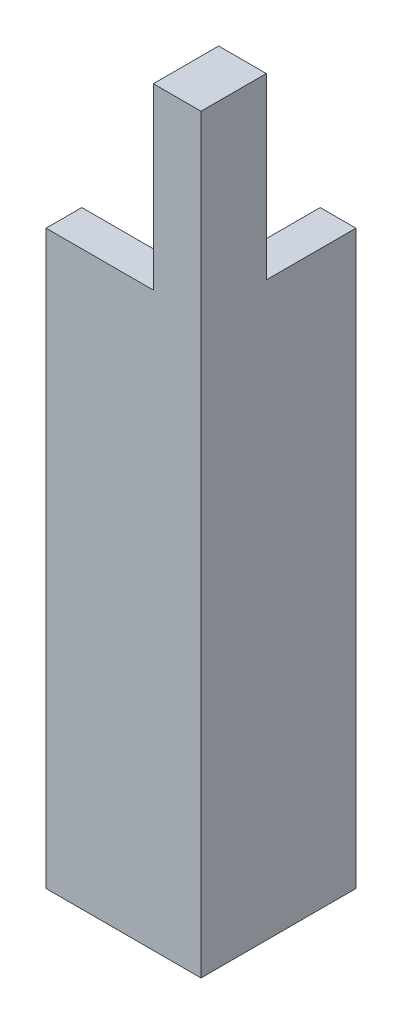
SolidWorks part; units mm, degrees
ref_plane "Alzado" through (0, 0, 0) normal (0, 0, 1) x (1, 0, 0)
ref_plane "Planta" through (0, 0, 0) normal (0, 1, 0) x (1, 0, 0)
ref_plane "Vista lateral" through (0, 0, 0) normal (1, 0, 0) x (0, 0, -1)
sketch "Croquis1" plane through (0, 0, 0) normal (0, 1, 0) x (1, 0, 0)
  line L0 (0, 0) -> (13, 0)
  line L1 (13, 0) -> (13, 13)
  line L2 (13, 13) -> (10, 13)
  line L3 (10, 13) -> (10, 3)
  line L4 (10, 3) -> (0, 3)
  line L5 (0, 3) -> (0, 0)
  dimension "D1" = 3
  dimension "D2" = 10
extrude "Saliente-Extruir1" add sketch "Croquis1" along normal blind 48
sketch "Croquis3" plane through (0, 48, 0) normal (0, 1, 0) x (1, 0, 0)
  line L0 (0, 0) -> (13, 0) construction
  line L1 (9, 0) -> (13, 0)
  line L2 (9, 0) -> (9, 5.48)
  line L3 (9, 5.48) -> (13, 5.48)
  line L4 (13, 0) -> (13, 5.48)
  line L5 (13, 0) -> (13, 13) construction
  line L6 (10, 3) -> (0, 3) construction
  dimension "D1" = 2.48
  dimension "D2" = 4
extrude "Saliente-Extruir3" add sketch "Croquis3" along normal blind 15
fillet "Redondeo1" radius 2 2 edges at (9.5, 48, -3) (10, 48, -4.24)
